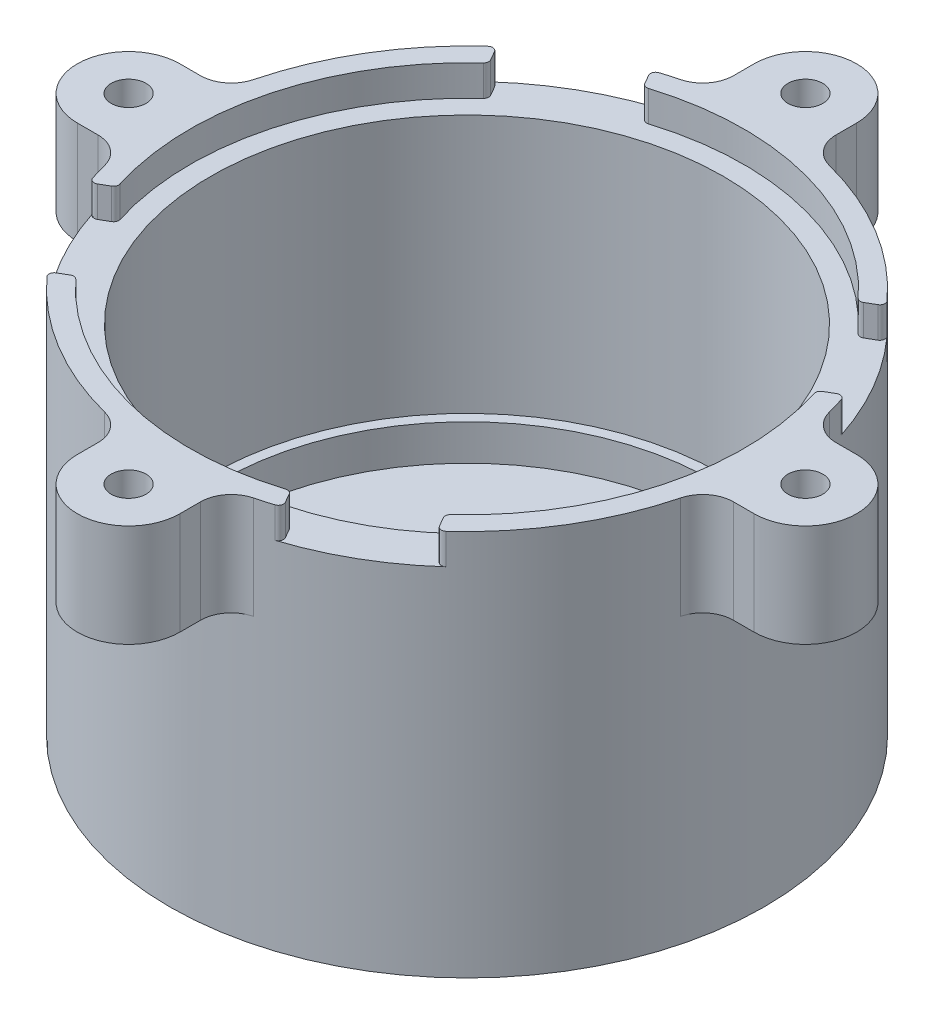
SolidWorks part; units mm, degrees
ref_plane "Plan de face" through (0, 0, 0) normal (0, 0, 1) x (1, 0, 0)
ref_plane "Plan de dessus" through (0, 0, 0) normal (0, 1, 0) x (1, 0, 0)
ref_plane "Plan de droite" through (0, 0, 0) normal (1, 0, 0) x (0, 0, -1)
sketch "Sketch1" plane through (0, 0, 0) normal (0, 0, 1) x (1, 0, 0)
  line L0 (0, 34.5752) -> (0, -31.3539) construction
  line L2 (29, -6) -> (29, 31.7)
  line L3 (29, 31.7) -> (27, 31.7)
  line L5 (25, 28.7) -> (25, 3.5)
  line L7 (5.5, -1) -> (5.5, -4)
  line L8 (25, 3.5) -> (24, 3.5)
  line L9 (24, 3.5) -> (24, 0)
  line L10 (24, 0) -> (6.5, 0)
  line L13 (29, -6) -> (4.25, -6)
  line L14 (25, 28.7) -> (27, 28.7)
  line L15 (27, 28.7) -> (27, 31.7)
  line L16 (4.25, -6) -> (4.25, -4)
  line L17 (4.25, -4) -> (5.5, -4)
  line L18 (5.5, -1) -> (6.5, 0)
  dimension "D1" = 25
  dimension "D3" = 45
  dimension "D4" = 25.2
  dimension "D5" = 3.5
  dimension "D6" = 1
  dimension "D7" = 4
  dimension "D8" = 2
  dimension "D9" = 3
  dimension "D10" = 3
  dimension "D11" = 5.5
  dimension "D12" = 4.25
  dimension "D13" = 2
  dimension "D16" = 24
revolve "Revolve1" add sketch "Sketch1" angle 360 about L0 region at (16.625, -5.549, 0)
sketch "Esquisse1" plane through (0, 31.7, 0) normal (0, 1, 0) x (1, 0, 0)
  line L0 (5, 33) -> (5, 28.5657)
  line L1 (-5, 33) -> (-5, 28.5657)
  arc A0 (5, 33) -> (-5, 33) centre (0, 33) ccw
  circle A1 centre (0, 33) radius 2.4
  arc A2 (-5, 28.5657) -> (5, 28.5657) centre (0, 0) cw
  circle A3 centre (0, 0) radius 29 construction
  circle A4 centre (0, 33) radius 1.7 construction
  circle M4 centre (0, 0) radius 29
  dimension "D1" = 4.8
  dimension "D2" = 10
  dimension "D4" = 3.4
  dimension "D3" = 33
extrude "Boss.-Extru.1" add sketch "Esquisse1" against normal blind 10 contours L0 A0 L1 A1 M4 region at (4.8625, 31.7, -30.7829)
extrude "Boss.-Extru.2" add sketch "Esquisse1<3>" against normal blind 4 contours A1 A4 region at (0, 31.7, -33)
sketch "Esquisse1<3>" plane through (0, 31.7, 0) normal (0, 1, 0) x (1, 0, 0) same geometry as "Esquisse1"
chamfer "Chanfrein2" distance 0.5 angle 45 1 edges at (0, 21.7, -30.6)
fillet "Congé1" radius 3 2 edges at (5, 26.7, -28.5657) (-5, 26.7, -28.5657)
pattern_circular "Répétition circulaire1" count 4 over 360 about axis through (0, 34.5752, 0) along (0, 1, 0) of "Boss.-Extru.1", "Congé1", "Boss.-Extru.2", "Chanfrein2"
sketch "Esquisse4" plane through (0, 31.7, 0) normal (0, 1, 0) x (1, 0, 0)
  point P0 (0, 33)
  point P3 (33, 0)
  point P6 (0, -33)
  point P9 (-33, 0)
hole_wizard "M3 Clearance Hole1" positions "Esquisse4" profile "Esquisse3" hole size "M3" standard "ANSI Metric" end condition through all
sketch "Esquisse3" plane through (0, 31.7, -33) normal (1, 0, 0) x (0, 0, 1)
  line L0 (0, 0) -> (0, 37.7)
  line L1 (0, 37.7) -> (1.7, 37.7)
  line L2 (1.7, 37.7) -> (1.7, 0)
  line L5 (1.7, 0) -> (0, 0)
  line L11 (0, -6.35) -> (0, 107.95) construction
  dimension "Thru Hole Dia." = 3.4
  dimension "Thru Hole Depth" = 37.7
sketch "Esquisse5" plane through (0, 31.7, 0) normal (0, 1, 0) x (1, 0, 0)
  line L0 (0, 0) -> (0, 38) construction
  line L1 (0, 0) -> (7.5058, 28.0118) construction
  line L2 (0, 0) -> (25.1147, 14.5) construction
  line L3 (25.6424, 8.4538) -> (27.4089, 9.4737)
  line L4 (20.1424, 17.9801) -> (21.9089, 19)
  line L5 (21.0257, 18.49) -> (26.5257, 8.9637) construction
  line L6 (0, 0) -> (14.5, -25.1147) construction
  line L7 (8.4538, -25.6424) -> (9.4737, -27.4089)
  line L8 (18.49, -21.0257) -> (8.9637, -26.5257) construction
  line L9 (17.9801, -20.1424) -> (19, -21.9089)
  line L10 (0, 0) -> (-25.1147, -14.5) construction
  line L11 (-25.6424, -8.4538) -> (-27.4089, -9.4737)
  line L12 (-21.0257, -18.49) -> (-26.5257, -8.9637) construction
  line L13 (-20.1424, -17.9801) -> (-21.9089, -19)
  line L14 (0, 0) -> (-14.5, 25.1147) construction
  line L15 (-8.4538, 25.6424) -> (-9.4737, 27.4089)
  line L16 (-18.49, 21.0257) -> (-8.9637, 26.5257) construction
  line L17 (-17.9801, 20.1424) -> (-19, 21.9089)
  arc A0 (5, 33) -> (-5, 33) centre (0, 33) ccw construction
  arc A1 (28.0791, 7.25) -> (7.25, 28.0791) centre (0, 0) ccw construction
  circle A3 centre (0, 0) radius 27 construction
  circle A4 centre (0, 0) radius 27 construction
  arc A5 (20.1424, 17.9801) -> (25.6424, 8.4538) centre (0, 0) cw
  arc A6 (21.9089, 19) -> (27.4089, 9.4737) centre (0, 0) cw
  arc A7 (17.9801, -20.1424) -> (8.4538, -25.6424) centre (0, 0) cw
  arc A8 (19, -21.9089) -> (9.4737, -27.4089) centre (0, 0) cw
  arc A9 (-20.1424, -17.9801) -> (-25.6424, -8.4538) centre (0, 0) cw
  arc A10 (-21.9089, -19) -> (-27.4089, -9.4737) centre (0, 0) cw
  arc A11 (-17.9801, 20.1424) -> (-8.4538, 25.6424) centre (0, 0) cw
  arc A12 (-19, 21.9089) -> (-9.4737, 27.4089) centre (0, 0) cw
  point P21 (23.7757, 13.7269)
  point P46 (0, 0)
  dimension "D4" = 4
  dimension "D1" = 15
  dimension "D2" = 45
  dimension "D3" = 11
extrude "Enlèv. mat.-Extru.1" cut sketch "Esquisse5" against normal up to surface (3 mm away) up to face at (0, 28.7, 27)
fillet "Congé2" radius 0.5 16 edges at (21.9089, 30.2, -19) (20.1424, 30.2, -17.9801) (27.4089, 30.2, -9.4737) (25.6424, 30.2, -8.4538) (19, 30.2, 21.9089) (17.9801, 30.2, 20.1424) (9.4737, 30.2, 27.4089) (8.4538, 30.2, 25.6424) (-21.9089, 30.2, 19) (-20.1424, 30.2, 17.9801) (-27.4089, 30.2, 9.4737) (-25.6424, 30.2, 8.4538) (-19, 30.2, -21.9089) (-17.9801, 30.2, -20.1424) (-9.4737, 30.2, -27.4089) (-8.4538, 30.2, -25.6424)
